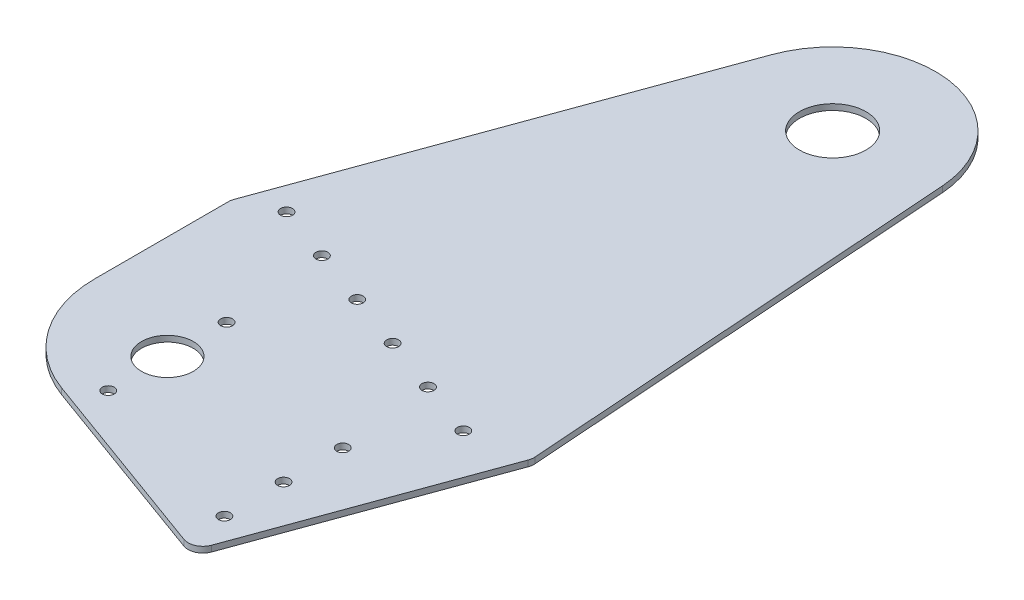
SolidWorks part; units mm, degrees
material "5052-H32"
ref_plane "Front Plane" through (0, 0, 0) normal (0, 0, 1) x (1, 0, 0)
ref_plane "Top Plane" through (0, 0, 0) normal (0, 1, 0) x (1, 0, 0)
ref_plane "Right Plane" through (0, 0, 0) normal (1, 0, 0) x (0, 0, -1)
sketch "Sketch1" plane through (0, 0, 0) normal (0, 1, 0) x (1, 0, 0)
  line L2 (0, 79.9615) -> (0, 137.226)
  line L3 (160.847, 106.8323) -> (8.6873, 162.2139) construction
  line L9 (124.1351, 5.967) -> (160.3844, 105.5611)
  line L11 (0, 138.3457) -> (152.1597, 82.9641) construction
  line L12 (4.3437, 150.2798) -> (156.5034, 94.8982) construction
  line L13 (116.079, 82.9641) -> (116.079, 0) construction
  line L14 (128.779, 6.7641) -> (103.379, 6.7641) construction
  line L15 (128.779, 6.7641) -> (128.779, 82.9641) construction
  line L16 (128.779, 82.9641) -> (103.379, 82.9641) construction
  line L17 (103.379, 6.7641) -> (103.379, 82.9641) construction
  line L18 (128.779, 6.7641) -> (103.379, 82.9641) construction
  line L19 (128.779, 82.9641) -> (103.379, 6.7641) construction
  line L20 (0.383, 139.3979) -> (8.6873, 162.2139)
  line L21 (8.6873, 162.2139) -> (61.8971, 308.4066)
  line L22 (147.4128, 296.4285) -> (160.7514, 108.1817)
  line L23 (33.4254, 32.2252) -> (115.9962, 2.1718)
  line L24 (0, 0) -> (121.9633, 0) construction
  circle A0 centre (103.379, 293.3084) radius 14.2875
  circle A1 centre (44.45, 66.6217) radius 11.1125
  circle A2 centre (44.45, 66.6217) radius 25.4 construction
  circle A3 centre (44.45, 92.0217) radius 2.5527
  circle A4 centre (44.45, 41.2217) radius 2.5527
  circle A5 centre (44.45, 66.6217) radius 31.75 construction
  arc A6 (147.4128, 296.4285) -> (61.8971, 308.4066) centre (103.379, 293.3084) ccw
  arc A9 (0.383, 139.3979) -> (0, 137.226) centre (6.35, 137.226) ccw
  arc A10 (160.3844, 105.5611) -> (160.7514, 108.1817) centre (154.4173, 107.7329) ccw
  arc A11 (115.9962, 2.1718) -> (124.1351, 5.967) centre (118.168, 8.1389) ccw
  arc A12 (0, 79.9615) -> (33.4254, 32.2252) centre (50.8, 79.9615) ccw
  point P3 (111.7505, 111.1869)
  point P14 (135.6187, 102.4996)
  point P20 (116.079, 44.8641)
  point P24 (87.8823, 119.8742)
  point P26 (64.0141, 128.5615)
  point P28 (40.1459, 137.2488)
  point P29 (116.079, 19.4641)
  point P32 (16.2778, 145.9362)
  point P42 (0, 0)
  point P49 (116.079, 70.2641)
  dimension "D2" = 28.575
  dimension "D3" = 22.225
  dimension "D4" = 50.8
  dimension "D5" = 5.1054
  dimension "D21" = 63.5
  dimension "D22" = 6.35
  dimension "D26" = 50.8
  dimension "D6" = 20
  dimension "D7" = 25.4
  dimension "D8" = 23.3807
  dimension "D9" = 161.925
  dimension "D10" = 25.4
  dimension "D11" = 12.7
  dimension "D12" = 155.575
  dimension "D13" = 25.4
  dimension "D14" = 25.4
  dimension "D15" = 25.4
  dimension "D16" = 25.4
  dimension "D17" = 234.221
  dimension "D18" = 44.45
  dimension "D19" = 25.4
  dimension "D20" = 76.2
  dimension "D23" = 25.4
  dimension "D24" = 25.4
  dimension "D25" = 12.7
  dimension "D27" = 77.5957
extrude "Boss-Extrude1" add sketch "Sketch1" along normal blind 2.54
hole_wizard "#7 (0.201) Diameter Hole1" positions "Sketch2" profile "Sketch3" hole size "#7" standard "ANSI Inch" end condition through all
sketch "Sketch2" plane through (0, 0, 0) normal (0, -1, 0) x (-1, 0, 0)
  point P0 (-135.6187, 102.4996)
  point P3 (-111.7505, 111.1869)
  point P6 (-87.8823, 119.8742)
  point P9 (-64.0141, 128.5615)
  point P12 (-40.1459, 137.2488)
  point P15 (-16.2778, 145.9362)
  point P18 (-116.079, 70.2641)
  point P21 (-116.079, 44.8641)
  point P24 (-116.079, 19.4641)
sketch "Sketch3" plane through (135.6187, 0, -102.4996) normal (1, 0, 0) x (0, 0, -1)
  line L0 (0, 0) -> (0, 2.54)
  line L1 (0, 2.54) -> (2.5527, 2.54)
  line L2 (2.5527, 2.54) -> (2.5527, 0)
  line L5 (2.5527, 0) -> (0, 0)
  line L11 (0, -6.35) -> (0, 107.95) construction
  dimension "Thru Hole Dia." = 5.1054
  dimension "Thru Hole Depth" = 2.54
sketch "Sketch7" [suppressed] plane through (0, 3.175, 0) normal (0, 1, 0) x (1, 0, 0)
  line L0 (62.0761, 169.3899) -> (62.5144, 170.567)
  line L1 (62.5144, 170.567) -> (61.5867, 170.2622)
  line L2 (66.9677, 175.195) -> (66.4796, 174.6886)
  line L3 (79.1731, 159.2722) -> (81.2123, 160.0556)
  line L4 (81.2123, 160.0556) -> (81.5639, 159.3016)
  line L5 (115.2098, 163.8413) -> (116.357, 163.4486)
  line L6 (116.357, 163.4486) -> (115.8813, 162.1889)
  line L7 (107.7827, 167.4695) -> (106.2875, 167.7994)
  line L8 (106.2875, 167.7994) -> (107.2664, 168.7114)
  line L9 (96.7548, 171.953) -> (96.1723, 172.7991)
  line L10 (96.1723, 172.7991) -> (95.6669, 171.9454)
  line L11 (100.3403, 166.7321) -> (97.6686, 163.2228)
  line L12 (89.4476, 166.3552) -> (91.3642, 168.2161)
  line L13 (91.3642, 168.2161) -> (90.6316, 168.886)
  line L14 (14.1169, 177.1315) -> (159.6183, 124.1733) construction
  line L15 (61.8971, 308.4066) -> (0.383, 139.3979) construction
  line L16 (160.7514, 108.1817) -> (147.4128, 296.4285) construction
  line L17 (33.4254, 32.2252) -> (115.9962, 2.1718) construction
  arc A0 (74.3082, 182.8504) -> (73.725, 182.5147) centre (74.7103, 181.4774) ccw
  arc A1 (73.725, 182.5147) -> (72.1718, 181.0017) centre (133.1992, 119.9033) ccw
  arc A2 (72.1718, 181.0017) -> (70.5314, 179.2921) centre (111.5899, 141.5378) ccw
  arc A3 (70.5314, 179.2921) -> (69.0762, 177.6244) centre (101.8392, 150.5038) ccw
  arc A4 (68.547, 177.0625) -> (69.0762, 177.6244) centre (64.4257, 181.474) ccw
  arc A5 (68.1985, 176.9514) -> (68.547, 177.0625) centre (68.2556, 177.3744) ccw
  arc A6 (67.7948, 177.1281) -> (68.1985, 176.9514) centre (68.3059, 177.7466) ccw
  arc A7 (66.8738, 177.9219) -> (67.7948, 177.1281) centre (86.4277, 199.6753) ccw
  arc A8 (66.8738, 177.9219) -> (65.9604, 178.4972) centre (64.7429, 175.5513) ccw
  arc A9 (65.9604, 178.4972) -> (64.9049, 178.7371) centre (64.7273, 175.5134) ccw
  arc A10 (64.9049, 178.7371) -> (63.6726, 178.6312) centre (64.6624, 174.336) ccw
  arc A11 (63.6726, 178.6312) -> (62.2317, 178.1778) centre (65.8385, 169.232) ccw
  arc A12 (62.2317, 178.1778) -> (60.6707, 177.4551) centre (68.6224, 162.3269) ccw
  arc A13 (60.6707, 177.4551) -> (59.5301, 176.703) centre (63.8858, 171.3384) ccw
  arc A14 (59.5301, 176.703) -> (58.5257, 175.7167) centre (64.2391, 170.9033) ccw
  arc A15 (58.5257, 175.7167) -> (57.3864, 174.2438) centre (75.6018, 161.3305) ccw
  arc A16 (56.7062, 173.3435) -> (57.3864, 174.2438) centre (42.2162, 184.9983) ccw
  arc A17 (56.1228, 172.7101) -> (56.7062, 173.3435) centre (51.6914, 177.3771) ccw
  arc A18 (55.5639, 172.2634) -> (56.1228, 172.7101) centre (53.2294, 175.7573) ccw
  arc A19 (54.9666, 171.9461) -> (55.5639, 172.2634) centre (53.6962, 175.0587) ccw
  arc A20 (54.5243, 171.7924) -> (54.9666, 171.9461) centre (53.293, 176.0466) ccw
  arc A21 (54.1163, 171.7066) -> (54.5243, 171.7924) centre (53.7472, 174.4772) ccw
  arc A22 (53.7901, 171.6904) -> (54.1163, 171.7066) centre (53.8553, 173.6659) ccw
  arc A23 (53.635, 171.7688) -> (53.7901, 171.6904) centre (53.7969, 171.8965) ccw
  arc A24 (53.5905, 172.1698) -> (53.635, 171.7688) centre (53.9344, 172.005) ccw
  arc A25 (54.0093, 172.8651) -> (53.5905, 172.1698) centre (57.4392, 170.3253) ccw
  arc A26 (54.9177, 173.9796) -> (54.0093, 172.8651) centre (66.4395, 163.6605) ccw
  arc A27 (56.8324, 176.0866) -> (54.9177, 173.9796) centre (201.8255, 42.4065) ccw
  arc A28 (56.8324, 176.0866) -> (58.6294, 178.1211) centre (10.0366, 219.2312) ccw
  arc A29 (58.6294, 178.1211) -> (59.308, 179.2325) centre (55.3883, 180.8631) ccw
  arc A30 (59.308, 179.2325) -> (59.3329, 180.0542) centre (58.2421, 179.6759) ccw
  arc A31 (59.3329, 180.0542) -> (58.8124, 180.8462) centre (57.5061, 179.4207) ccw
  arc A32 (58.8124, 180.8462) -> (57.7553, 181.5045) centre (56.5222, 178.3469) ccw
  arc A33 (57.7553, 181.5045) -> (56.6586, 181.6278) centre (56.9757, 179.5081) ccw
  arc A34 (56.6586, 181.6278) -> (55.3092, 181.1821) centre (57.2782, 177.4858) ccw
  arc A35 (55.3092, 181.1821) -> (53.3754, 180.0329) centre (66.6249, 159.9392) ccw
  arc A36 (50.4555, 178.11) -> (53.3754, 180.0329) centre (-1623.116, 2722.5471) ccw
  arc A37 (49.9624, 177.8143) -> (50.4555, 178.11) centre (46.648, 183.8988) ccw
  arc A38 (49.9101, 177.875) -> (49.9624, 177.8143) centre (49.9428, 177.8503) ccw
  arc A39 (50.3128, 178.3647) -> (49.9101, 177.875) centre (56.008, 173.2696) ccw
  arc A40 (50.6868, 178.776) -> (50.3128, 178.3647) centre (76.0211, 155.3656) ccw
  arc A41 (51.2355, 179.3665) -> (50.6868, 178.776) centre (157.5463, 80.0316) ccw
  arc A42 (51.843, 180.0132) -> (51.2355, 179.3665) centre (169.196, 69.1464) ccw
  arc A43 (52.4254, 180.6256) -> (51.843, 180.0132) centre (148.4427, 88.7526) ccw
  arc A44 (52.4254, 180.6256) -> (53.4057, 181.7377) centre (39.3118, 193.1732) ccw
  arc A45 (53.4057, 181.7377) -> (53.5985, 182.3391) centre (52.73, 182.286) ccw
  arc A46 (53.5985, 182.3391) -> (53.3133, 182.8365) centre (52.9532, 182.2996) ccw
  arc A47 (53.3133, 182.8365) -> (52.2525, 183.4524) centre (48.0293, 174.9565) ccw
  arc A48 (52.2525, 183.4524) -> (51.5201, 183.784) centre (47.2947, 173.4787) ccw
  arc A49 (51.5201, 183.784) -> (51.1138, 183.8533) centre (51.1621, 182.911) ccw
  arc A50 (51.1138, 183.8533) -> (50.7464, 183.7367) centre (51.1527, 183.0936) ccw
  arc A51 (50.7464, 183.7367) -> (50.2, 183.3471) centre (53.9544, 178.6599) ccw
  arc A52 (50.2, 183.3471) -> (49.7518, 182.9327) centre (52.8985, 179.9782) ccw
  arc A53 (49.7518, 182.9327) -> (49.0516, 182.1629) centre (73.6142, 160.5277) ccw
  arc A54 (49.0516, 182.1629) -> (48.2702, 181.2458) centre (76.593, 157.9039) ccw
  arc A55 (48.2702, 181.2458) -> (47.5086, 180.2915) centre (78.2622, 156.5282) ccw
  arc A56 (46.4851, 179.0185) -> (47.5086, 180.2915) centre (14.0592, 206.1378) ccw
  arc A57 (45.7613, 178.2653) -> (46.4851, 179.0185) centre (40.6676, 183.884) ccw
  arc A58 (45.0854, 177.7635) -> (45.7613, 178.2653) centre (42.8654, 181.4597) ccw
  arc A59 (44.2716, 177.3569) -> (45.0854, 177.7635) centre (42.0649, 182.7925) ccw
  arc A60 (42.4079, 176.7566) -> (44.2716, 177.3569) centre (39.29, 189.6277) ccw
  arc A61 (40.9063, 176.6373) -> (42.4079, 176.7566) centre (41.2837, 181.3973) ccw
  arc A62 (39.9018, 176.9889) -> (40.9063, 176.6373) centre (41.0714, 178.7199) ccw
  arc A63 (39.431, 177.7408) -> (39.9018, 176.9889) centre (40.5148, 177.8961) ccw
  arc A64 (39.5246, 178.6802) -> (39.431, 177.7408) centre (41.3834, 178.0206) ccw
  arc A65 (40.1422, 180.1498) -> (39.5246, 178.6802) centre (52.749, 173.9875) ccw
  arc A66 (40.967, 181.6069) -> (40.1422, 180.1498) centre (52.5933, 174.0636) ccw
  arc A67 (41.8093, 182.6065) -> (40.967, 181.6069) centre (45.3757, 178.7465) ccw
  arc A68 (42.735, 183.3116) -> (41.8093, 182.6065) centre (45.9761, 178.0966) ccw
  arc A69 (43.9637, 183.9848) -> (42.735, 183.3116) centre (49.4769, 172.4638) ccw
  arc A70 (45.1396, 184.492) -> (43.9637, 183.9848) centre (51.0302, 169.2179) ccw
  arc A71 (45.4706, 184.3586) -> (45.1396, 184.492) centre (45.2337, 184.2481) ccw
  arc A72 (45.4918, 184.1987) -> (45.4706, 184.3586) centre (45.2267, 184.2448) ccw
  arc A73 (45.4167, 183.8436) -> (45.4918, 184.1987) centre (40.5531, 185.0579) ccw
  arc A74 (45.2918, 183.4176) -> (45.4167, 183.8436) centre (40.1115, 185.1681) ccw
  arc A75 (45.1216, 182.9606) -> (45.2918, 183.4176) centre (37.7577, 185.9635) ccw
  arc A76 (44.6747, 182.1439) -> (45.1216, 182.9606) centre (41.315, 184.5129) ccw
  arc A77 (44.0662, 181.4742) -> (44.6747, 182.1439) centre (41.6698, 184.2628) ccw
  arc A78 (43.3406, 180.9981) -> (44.0662, 181.4742) centre (41.872, 184.0274) ccw
  arc A79 (42.5496, 180.7503) -> (43.3406, 180.9981) centre (42.1132, 183.5299) ccw
  arc A80 (42.5496, 180.7503) -> (42.0333, 180.6322) centre (43.1444, 176.9613) ccw
  arc A81 (42.0333, 180.6322) -> (41.6424, 180.4565) centre (42.5179, 179.0313) ccw
  arc A82 (41.6424, 180.4565) -> (41.3631, 180.2173) centre (42.2562, 179.4572) ccw
  arc A83 (41.3631, 180.2173) -> (41.1817, 179.91) centre (42.1574, 179.5413) ccw
  arc A84 (41.1817, 179.91) -> (41.3098, 179.5404) centre (41.4675, 179.802) ccw
  arc A85 (41.3098, 179.5404) -> (42.0184, 179.2356) centre (42.7766, 181.9744) ccw
  arc A86 (42.0184, 179.2356) -> (42.9911, 179.0785) centre (43.2169, 183.5653) ccw
  arc A87 (42.9911, 179.0785) -> (43.9333, 179.1484) centre (43.1825, 182.8819) ccw
  arc A88 (43.9333, 179.1484) -> (44.9037, 179.5156) centre (43.3041, 182.2773) ccw
  arc A89 (44.9037, 179.5156) -> (45.7482, 180.1858) centre (43.0455, 182.7238) ccw
  arc A90 (45.7482, 180.1858) -> (46.4656, 181.1717) centre (42.1809, 183.5357) ccw
  arc A91 (46.4656, 181.1717) -> (47.0588, 182.4767) centre (38.3652, 185.6409) ccw
  arc A92 (47.0588, 182.4767) -> (47.3717, 183.6741) centre (40.8285, 184.7444) ccw
  arc A93 (47.3717, 183.6741) -> (47.3128, 184.5787) centre (45.3846, 183.9991) ccw
  arc A94 (47.3128, 184.5787) -> (46.8711, 185.315) centre (45.6402, 184.0759) ccw
  arc A95 (46.8711, 185.315) -> (46.0042, 185.9854) centre (43.743, 182.166) ccw
  arc A96 (46.0042, 185.9854) -> (43.5248, 186.5796) centre (43.802, 182.2657) ccw
  arc A97 (43.5248, 186.5796) -> (40.6936, 185.808) centre (43.994, 179.2776) ccw
  arc A98 (40.6936, 185.808) -> (38.0435, 183.8254) centre (44.996, 177.2948) ccw
  arc A99 (38.0435, 183.8254) -> (36.1073, 180.9839) centre (46.1106, 176.2478) ccw
  arc A100 (35.7666, 180.3077) -> (36.1073, 180.9839) centre (22.1662, 187.5841) ccw
  arc A101 (35.4405, 179.7525) -> (35.7666, 180.3077) centre (28.6157, 184.1336) ccw
  arc A102 (35.1529, 179.3322) -> (35.4405, 179.7525) centre (28.1525, 184.4309) ccw
  arc A103 (35.0212, 179.292) -> (35.1529, 179.3322) centre (35.0603, 179.3996) ccw
  arc A104 (34.8987, 179.3634) -> (35.0212, 179.292) centre (35.1574, 179.6664) ccw
  arc A105 (34.7135, 179.5337) -> (34.8987, 179.3634) centre (37.1267, 181.9726) ccw
  arc A106 (34.5102, 179.7505) -> (34.7135, 179.5337) centre (37.4991, 182.3489) ccw
  arc A107 (34.3152, 179.9906) -> (34.5102, 179.7505) centre (38.0148, 182.7973) ccw
  arc A108 (34.3152, 179.9906) -> (33.9923, 180.3441) centre (32.2157, 178.3978) ccw
  arc A109 (33.9923, 180.3441) -> (33.1472, 181.1013) centre (-7.0589, 135.3727) ccw
  arc A110 (33.1472, 181.1013) -> (32.12, 181.9836) centre (-5.5235, 137.119) ccw
  arc A111 (32.12, 181.9836) -> (30.9902, 182.914) centre (-19.1906, 120.8302) ccw
  arc A112 (29.8644, 183.859) -> (30.9902, 182.914) centre (55.91, 213.7448) ccw
  arc A113 (28.849, 184.7853) -> (29.8644, 183.859) centre (49.7895, 206.7219) ccw
  arc A114 (28.0329, 185.5958) -> (28.849, 184.7853) centre (48.8821, 205.7713) ccw
  arc A115 (27.72, 186.0357) -> (28.0329, 185.5958) centre (29.3248, 186.846) ccw
  arc A116 (27.5634, 187.404) -> (27.72, 186.0357) centre (29.4953, 186.932) ccw
  arc A117 (28.2937, 188.8328) -> (27.5634, 187.404) centre (30.9404, 186.579) ccw
  arc A118 (29.9235, 190.2307) -> (28.2937, 188.8328) centre (33.5403, 184.365) ccw
  arc A119 (32.3635, 191.4887) -> (29.9235, 190.2307) centre (39.3462, 174.9492) ccw
  arc A120 (34.2055, 192.0999) -> (32.3635, 191.4887) centre (37.1375, 180.1808) ccw
  arc A121 (36.2347, 192.4587) -> (34.2055, 192.0999) centre (37.9264, 176.974) ccw
  arc A122 (38.0495, 192.5388) -> (36.2347, 192.4587) centre (37.761, 178.4879) ccw
  arc A123 (39.0536, 192.2197) -> (38.0495, 192.5388) centre (38.0113, 190.6797) ccw
  arc A124 (39.401, 191.9318) -> (39.0536, 192.2197) centre (37.7469, 190.289) ccw
  arc A125 (39.5146, 191.678) -> (39.401, 191.9318) centre (39.1218, 191.6545) ccw
  arc A126 (39.4565, 191.3418) -> (39.5146, 191.678) centre (38.7713, 191.6335) ccw
  arc A127 (39.1465, 190.6692) -> (39.4565, 191.3418) centre (27.8847, 196.2671) ccw
  arc A128 (38.0069, 188.9592) -> (39.1465, 190.6692) centre (31.8572, 194.2925) ccw
  arc A129 (36.3742, 187.4082) -> (38.0069, 188.9592) centre (29.1898, 196.6058) ccw
  arc A130 (34.4963, 186.2162) -> (36.3742, 187.4082) centre (29.3429, 196.4098) ccw
  arc A131 (32.6257, 185.5753) -> (34.4963, 186.2162) centre (31.2535, 192.6306) ccw
  arc A132 (32.6257, 185.5753) -> (32.326, 185.4734) centre (32.849, 184.4267) ccw
  arc A133 (32.326, 185.4734) -> (32.1971, 185.3132) centre (32.4364, 185.2526) ccw
  arc A134 (32.1971, 185.3132) -> (32.187, 185.0278) centre (32.8524, 185.1473) ccw
  arc A135 (32.187, 185.0278) -> (32.3205, 184.3701) centre (46.8553, 187.6615) ccw
  arc A136 (32.3205, 184.3701) -> (32.6327, 183.5397) centre (35.4909, 185.088) ccw
  arc A137 (32.6327, 183.5397) -> (33.1345, 182.9292) centre (34.4573, 184.5281) ccw
  arc A138 (33.1345, 182.9292) -> (33.7845, 182.5919) centre (34.2412, 184.2668) ccw
  arc A139 (33.7845, 182.5919) -> (34.5255, 182.546) centre (34.2659, 184.3575) ccw
  arc A140 (34.5255, 182.546) -> (36.1223, 183.2401) centre (34.0587, 185.8032) ccw
  arc A141 (36.1223, 183.2401) -> (38.2538, 185.2006) centre (22.3005, 200.4074) ccw
  arc A142 (38.2538, 185.2006) -> (40.2061, 187.5541) centre (22.1985, 200.5047) ccw
  arc A143 (40.2061, 187.5541) -> (41.3352, 189.6901) centre (33.0357, 192.7108) ccw
  arc A144 (41.3352, 189.6901) -> (41.6737, 191.3689) centre (35.9537, 191.6488) ccw
  arc A145 (41.6737, 191.3689) -> (41.4198, 192.8507) centre (38.2108, 191.5384) ccw
  arc A146 (41.4198, 192.8507) -> (40.543, 194.1499) centre (37.865, 191.397) ccw
  arc A147 (40.543, 194.1499) -> (39.0445, 195.2909) centre (35.0939, 188.5481) ccw
  arc A148 (39.0445, 195.2909) -> (36.5392, 195.9699) centre (36.5427, 191.021) ccw
  arc A149 (36.5392, 195.9699) -> (32.9739, 195.586) centre (36.5513, 179.1093) ccw
  arc A150 (32.9739, 195.586) -> (29.3635, 194.3985) centre (36.8595, 177.6898) ccw
  arc A151 (29.3635, 194.3985) -> (26.6543, 192.6008) centre (33.4359, 185.3211) ccw
  arc A152 (26.6543, 192.6008) -> (24.9307, 190.1375) centre (31.5632, 187.3313) ccw
  arc A153 (24.9307, 190.1375) -> (24.6835, 187.5211) centre (28.9468, 188.4382) ccw
  arc A154 (24.6835, 187.5211) -> (26.0207, 184.7839) centre (30.8844, 188.8551) ccw
  arc A155 (26.0207, 184.7839) -> (28.9405, 181.9734) centre (40.4964, 196.9008) ccw
  arc A156 (29.9885, 181.128) -> (28.9405, 181.9734) centre (8.4014, 155.4417) ccw
  arc A157 (30.3575, 180.6787) -> (29.9885, 181.128) centre (28.9675, 179.9132) ccw
  arc A158 (30.3713, 180.3133) -> (30.3575, 180.6787) centre (30.0009, 180.4823) ccw
  arc A159 (30.0759, 179.9118) -> (30.3713, 180.3133) centre (29.2641, 180.8183) ccw
  arc A160 (28.5512, 179.2654) -> (30.0759, 179.9118) centre (28.3681, 181.8189) ccw
  arc A161 (25.8887, 179.3109) -> (28.5512, 179.2654) centre (27.4758, 194.2586) ccw
  arc A162 (23.2563, 179.8312) -> (25.8887, 179.3109) centre (27.4762, 194.2617) ccw
  arc A163 (21.8803, 180.7864) -> (23.2563, 179.8312) centre (23.9984, 182.369) ccw
  arc A164 (21.8803, 180.7864) -> (21.4146, 181.3746) centre (11.131, 172.7548) ccw
  arc A165 (21.4146, 181.3746) -> (21.194, 181.4707) centre (21.208, 181.2014) ccw
  arc A166 (21.194, 181.4707) -> (20.9847, 181.3519) centre (21.2079, 181.2022) ccw
  arc A167 (20.9847, 181.3519) -> (20.5852, 180.7185) centre (32.0578, 173.9268) ccw
  arc A168 (20.5852, 180.7185) -> (20.5596, 178.2742) centre (22.6871, 179.4742) ccw
  arc A169 (20.5596, 178.2742) -> (22.7566, 176.3693) centre (24.3256, 180.3983) ccw
  arc A170 (22.7566, 176.3693) -> (26.8636, 175.665) centre (26.5339, 186.0688) ccw
  arc A171 (26.8636, 175.665) -> (31.4496, 176.4875) centre (26.3557, 191.6925) ccw
  arc A172 (32.2098, 176.7264) -> (31.4496, 176.4875) centre (38.1788, 156.4012) ccw
  arc A173 (33.0182, 176.9497) -> (32.2098, 176.7264) centre (39.5156, 151.8489) ccw
  arc A174 (33.7585, 177.1285) -> (33.0182, 176.9497) centre (38.8624, 154.3726) ccw
  arc A175 (34.2819, 177.2207) -> (33.7585, 177.1285) centre (35.0169, 171.5178) ccw
  arc A176 (34.9396, 177.2772) -> (34.2819, 177.2207) centre (35.2749, 169.5161) ccw
  arc A177 (35.2649, 177.2034) -> (34.9396, 177.2772) centre (34.967, 176.6436) ccw
  arc A178 (35.5206, 176.9724) -> (35.2649, 177.2034) centre (34.9322, 176.5782) ccw
  arc A179 (35.9024, 176.3582) -> (35.5206, 176.9724) centre (26.6812, 171.0512) ccw
  arc A180 (35.9024, 176.3582) -> (36.9988, 175.1864) centre (38.9535, 178.1142) ccw
  arc A181 (36.9988, 175.1864) -> (38.571, 174.5314) centre (39.4525, 178.8615) ccw
  arc A182 (38.571, 174.5314) -> (40.5484, 174.4493) centre (39.8152, 180.6435) ccw
  arc A183 (40.5484, 174.4493) -> (42.8178, 174.9505) centre (39.1738, 186.0622) ccw
  arc A184 (43.3201, 175.1069) -> (42.8178, 174.9505) centre (48.2695, 158.3264) ccw
  arc A185 (43.7701, 175.2291) -> (43.3201, 175.1069) centre (46.3835, 164.7208) ccw
  arc A186 (44.1476, 175.3175) -> (43.7701, 175.2291) centre (47.1628, 161.587) ccw
  arc A187 (44.2628, 175.3098) -> (44.1476, 175.3175) centre (44.192, 175.1153) ccw
  arc A188 (44.3107, 175.241) -> (44.2628, 175.3098) centre (44.2379, 175.2415) ccw
  arc A189 (44.2954, 175.0356) -> (44.3107, 175.241) centre (42.7889, 175.2514) ccw
  arc A190 (44.2393, 174.7674) -> (44.2954, 175.0356) centre (42.1713, 175.3398) ccw
  arc A191 (44.1412, 174.4607) -> (44.2393, 174.7674) centre (40.311, 175.8548) ccw
  arc A192 (44.1412, 174.4607) -> (44.0089, 173.708) centre (46.203, 173.7103) ccw
  arc A193 (44.0089, 173.708) -> (44.1385, 172.9419) centre (46.3511, 173.7104) ccw
  arc A194 (44.1385, 172.9419) -> (44.5028, 172.2883) centre (46.1785, 173.6505) ccw
  arc A195 (44.5028, 172.2883) -> (45.0452, 171.8581) centre (45.7458, 173.2987) ccw
  arc A196 (45.0452, 171.8581) -> (45.5046, 171.7887) centre (45.3862, 172.5592) ccw
  arc A197 (45.5046, 171.7887) -> (46.0003, 171.9763) centre (45.311, 173.0486) ccw
  arc A198 (46.0003, 171.9763) -> (46.7213, 172.5276) centre (42.9825, 176.6707) ccw
  arc A199 (46.7213, 172.5276) -> (48.1908, 173.8802) centre (-21.0634, 247.6437) ccw
  arc A200 (49.9531, 175.4754) -> (48.1908, 173.8802) centre (92.8617, 126.3005) ccw
  arc A201 (51.74, 176.975) -> (49.9531, 175.4754) centre (89.7982, 129.8115) ccw
  arc A202 (53.4092, 178.3032) -> (51.74, 176.975) centre (149.5534, 55.76) ccw
  arc A203 (53.7366, 178.3554) -> (53.4092, 178.3032) centre (53.6199, 178.0346) ccw
  arc A204 (53.756, 178.2996) -> (53.7366, 178.3554) centre (53.7236, 178.3196) ccw
  arc A205 (53.4455, 177.8028) -> (53.756, 178.2996) centre (14.1169, 202.725) ccw
  arc A206 (53.0612, 177.2191) -> (53.4455, 177.8028) centre (36.5165, 188.5306) ccw
  arc A207 (52.5822, 176.5337) -> (53.0612, 177.2191) centre (19.3352, 200.2773) ccw
  arc A208 (52.5822, 176.5337) -> (51.6189, 175.0333) centre (67.2678, 166.0458) ccw
  arc A209 (51.6189, 175.0333) -> (50.8843, 173.5493) centre (63.2726, 168.3404) ccw
  arc A210 (50.8843, 173.5493) -> (50.4332, 172.233) centre (60.3416, 169.5728) ccw
  arc A211 (50.4332, 172.233) -> (50.3764, 171.2877) centre (52.709, 171.622) ccw
  arc A212 (50.3764, 171.2877) -> (50.8293, 170.4134) centre (51.8564, 171.4998) ccw
  arc A213 (50.8293, 170.4134) -> (51.7794, 169.8973) centre (52.2752, 171.9427) ccw
  arc A214 (51.7794, 169.8973) -> (53.1461, 169.8276) centre (52.647, 173.4767) ccw
  arc A215 (53.1461, 169.8276) -> (54.7542, 170.2266) centre (52.0974, 177.4948) ccw
  arc A216 (55.3189, 170.4157) -> (54.7542, 170.2266) centre (58.4979, 159.9846) ccw
  arc A217 (55.6177, 170.4524) -> (55.3189, 170.4157) centre (55.573, 169.5819) ccw
  arc A218 (55.7691, 170.3669) -> (55.6177, 170.4524) centre (55.6077, 170.2581) ccw
  arc A219 (55.8258, 170.1715) -> (55.7691, 170.3669) centre (55.4927, 170.1806) ccw
  arc A220 (55.8258, 170.1715) -> (55.8514, 169.9319) centre (56.7312, 170.1468) ccw
  arc A221 (55.8514, 169.9319) -> (55.9579, 169.5508) centre (61.6551, 171.3493) ccw
  arc A222 (55.9579, 169.5508) -> (56.1102, 169.1191) centre (62.5193, 171.6221) ccw
  arc A223 (56.1102, 169.1191) -> (56.2928, 168.6924) centre (62.8661, 171.7576) ccw
  arc A224 (56.2928, 168.6924) -> (57.4829, 167.4515) centre (58.71, 169.8196) ccw
  arc A225 (57.4829, 167.4515) -> (59.2339, 167.1346) centre (58.8722, 170.1326) ccw
  arc A226 (59.2339, 167.1346) -> (60.9662, 167.8594) centre (58.8215, 170.5531) ccw
  arc A227 (60.9662, 167.8594) -> (62.0761, 169.3899) centre (58.7665, 170.6222) ccw
  arc A228 (60.6138, 170.7928) -> (61.5867, 170.2622) centre (61.3494, 170.9844) ccw
  arc A229 (60.8154, 172.4171) -> (60.6138, 170.7928) centre (62.7575, 171.3513) ccw
  arc A230 (62.6398, 174.8337) -> (60.8154, 172.4171) centre (70.0177, 167.367) ccw
  arc A231 (64.8718, 176.2485) -> (62.6398, 174.8337) centre (67.003, 170.418) ccw
  arc A232 (65.3282, 176.4029) -> (64.8718, 176.2485) centre (68.2976, 166.8761) ccw
  arc A233 (65.749, 176.5194) -> (65.3282, 176.4029) centre (67.3605, 169.8827) ccw
  arc A234 (66.1032, 176.5955) -> (65.749, 176.5194) centre (67.3446, 169.9483) ccw
  arc A235 (66.2518, 176.5832) -> (66.1032, 176.5955) centre (66.1551, 176.3175) ccw
  arc A236 (66.44, 176.4345) -> (66.2518, 176.5832) centre (66.1213, 176.2247) ccw
  arc A237 (66.7316, 175.9559) -> (66.44, 176.4345) centre (59.7592, 172.036) ccw
  arc A238 (66.9914, 175.457) -> (66.7316, 175.9559) centre (59.0868, 171.658) ccw
  arc A239 (67.0017, 175.2495) -> (66.9914, 175.457) centre (66.7501, 175.3411) ccw
  arc A240 (66.9677, 175.195) -> (67.0017, 175.2495) centre (66.8559, 175.3025) ccw
  arc A241 (65.9217, 174.1157) -> (66.4796, 174.6886) centre (-0.3358, 239.1998) ccw
  arc A242 (65.2645, 173.4503) -> (65.9217, 174.1157) centre (-57.3273, 295.182) ccw
  arc A243 (65.2645, 173.4503) -> (64.0677, 172.1499) centre (81.8084, 157.0225) ccw
  arc A244 (64.0677, 172.1499) -> (63.4286, 171.1774) centre (67.6274, 169.1145) ccw
  arc A245 (63.4286, 171.1774) -> (63.0742, 170.1165) centre (67.1785, 169.3351) ccw
  arc A246 (63.0742, 170.1165) -> (62.8538, 168.5433) centre (79.0298, 167.0787) ccw
  arc A247 (62.8538, 168.5433) -> (62.9704, 166.7394) centre (68.6902, 168.0148) ccw
  arc A248 (62.9704, 166.7394) -> (63.6889, 165.5617) centre (65.0575, 167.2048) ccw
  arc A249 (63.6889, 165.5617) -> (64.9741, 165.071) centre (65.0485, 167.194) ccw
  arc A250 (64.9741, 165.071) -> (66.7601, 165.2889) centre (65.1764, 170.8417) ccw
  arc A251 (67.3237, 165.441) -> (66.7601, 165.2889) centre (72.4207, 145.443) ccw
  arc A252 (67.8029, 165.5512) -> (67.3237, 165.441) centre (69.904, 155.3172) ccw
  arc A253 (68.2017, 165.6286) -> (67.8029, 165.5512) centre (71.5525, 147.2877) ccw
  arc A254 (68.2539, 165.5956) -> (68.2017, 165.6286) centre (68.2099, 165.5838) ccw
  arc A255 (68.2632, 165.5138) -> (68.2539, 165.5956) centre (67.9851, 165.5235) ccw
  arc A256 (68.2486, 165.1392) -> (68.2632, 165.5138) centre (18.2975, 167.2726) ccw
  arc A257 (68.2263, 164.699) -> (68.2486, 165.1392) centre (40.5629, 166.3217) ccw
  arc A258 (68.1942, 164.1979) -> (68.2263, 164.699) centre (21.7421, 167.4257) ccw
  arc A259 (68.1942, 164.1979) -> (68.2557, 162.9509) centre (73.4553, 163.8323) ccw
  arc A260 (68.2557, 162.9509) -> (68.6061, 161.6871) centre (74.5732, 164.0218) ccw
  arc A261 (68.6061, 161.6871) -> (69.1861, 160.5706) centre (74.1315, 163.849) ccw
  arc A262 (69.1861, 160.5706) -> (69.9292, 159.7637) centre (72.0774, 162.4873) ccw
  arc A263 (69.9292, 159.7637) -> (71.0506, 159.11) centre (72.8077, 163.4132) ccw
  arc A264 (71.0506, 159.11) -> (72.6135, 158.5966) centre (75.4812, 169.9608) ccw
  arc A265 (72.6135, 158.5966) -> (74.2686, 158.2998) centre (75.5651, 170.2933) ccw
  arc A266 (74.2686, 158.2998) -> (75.6874, 158.3104) centre (74.932, 164.4372) ccw
  arc A267 (75.6874, 158.3104) -> (76.3847, 158.4332) centre (74.8472, 165.1251) ccw
  arc A268 (76.3847, 158.4332) -> (77.308, 158.6665) centre (71.4689, 179.8295) ccw
  arc A269 (77.308, 158.6665) -> (78.2865, 158.9591) centre (70.9596, 181.6752) ccw
  arc A270 (78.2865, 158.9591) -> (79.1731, 159.2722) centre (73.0176, 175.2945) ccw
  arc A271 (81.5639, 159.3016) -> (82.0723, 158.5817) centre (83.8133, 160.3506) ccw
  arc A272 (82.0723, 158.5817) -> (82.8503, 157.998) centre (84.6282, 161.1785) ccw
  arc A273 (82.8503, 157.998) -> (83.7221, 157.6587) centre (84.503, 160.9544) ccw
  arc A274 (83.7221, 157.6587) -> (84.5041, 157.658) centre (84.1145, 159.3147) ccw
  arc A275 (84.5041, 157.658) -> (84.898, 157.7963) centre (84.055, 159.5674) ccw
  arc A276 (84.898, 157.7963) -> (85.4779, 158.094) centre (80.2438, 167.5753) ccw
  arc A277 (85.4779, 158.094) -> (86.1162, 158.4718) centre (79.4906, 168.9396) ccw
  arc A278 (86.1162, 158.4718) -> (86.7275, 158.8854) centre (79.669, 168.6578) ccw
  arc A279 (87.2967, 159.2808) -> (86.7275, 158.8854) centre (97.7406, 143.6379) ccw
  arc A280 (87.8098, 159.6034) -> (87.2967, 159.2808) centre (93.4193, 150.1105) ccw
  arc A281 (88.2441, 159.8499) -> (87.8098, 159.6034) centre (95.1182, 147.2354) ccw
  arc A282 (88.3811, 159.8626) -> (88.2441, 159.8499) centre (88.3273, 159.6972) ccw
  arc A283 (88.4414, 159.7807) -> (88.3811, 159.8626) centre (88.3541, 159.7795) ccw
  arc A284 (88.427, 159.5386) -> (88.4414, 159.7807) centre (86.7915, 159.7576) ccw
  arc A285 (88.3624, 159.22) -> (88.427, 159.5386) centre (86.0178, 159.8612) ccw
  arc A286 (88.2462, 158.8546) -> (88.3624, 159.22) centre (83.8571, 160.4521) ccw
  arc A287 (88.2462, 158.8546) -> (88.1272, 158.3962) centre (90.5899, 158.0016) ccw
  arc A288 (88.1272, 158.3962) -> (88.0913, 157.9067) centre (90.9602, 157.9422) ccw
  arc A289 (88.0913, 157.9067) -> (88.1393, 157.4142) centre (91.0105, 157.9429) ccw
  arc A290 (88.1393, 157.4142) -> (88.2697, 156.946) centre (90.8101, 157.906) ccw
  arc A291 (88.2697, 156.946) -> (88.5079, 156.4198) centre (92.5095, 158.5481) ccw
  arc A292 (88.5079, 156.4198) -> (88.7537, 156.1203) centre (89.3753, 156.8811) ccw
  arc A293 (88.7537, 156.1203) -> (89.0958, 155.9389) centre (89.378, 156.8844) ccw
  arc A294 (89.0958, 155.9389) -> (89.6608, 155.8086) centre (90.4086, 160.338) ccw
  arc A295 (89.6608, 155.8086) -> (90.1565, 155.7817) centre (90.0307, 158.0495) ccw
  arc A296 (90.1565, 155.7817) -> (90.8132, 155.8497) centre (89.7737, 162.6832) ccw
  arc A297 (90.8132, 155.8497) -> (91.5106, 155.9893) centre (89.6645, 163.4011) ccw
  arc A298 (91.5106, 155.9893) -> (92.1441, 156.1863) centre (90.1128, 161.6014) ccw
  arc A299 (93.2212, 156.5738) -> (92.1441, 156.1863) centre (107.0085, 116.5611) ccw
  arc A300 (93.653, 156.6471) -> (93.2212, 156.5738) centre (93.6592, 155.3025) ccw
  arc A301 (93.8054, 156.5151) -> (93.653, 156.6471) centre (93.6537, 156.494) ccw
  arc A302 (93.7714, 156.1938) -> (93.8054, 156.5151) centre (93.1422, 156.4228) ccw
  arc A303 (93.7714, 156.1938) -> (93.7529, 155.6122) centre (94.648, 155.8748) ccw
  arc A304 (93.7529, 155.6122) -> (94.0829, 154.8096) centre (97.7329, 156.7795) ccw
  arc A305 (94.0829, 154.8096) -> (94.5832, 154.0778) centre (97.8126, 156.8225) ccw
  arc A306 (94.5832, 154.0778) -> (95.112, 153.71) centre (95.5427, 154.8932) ccw
  arc A307 (95.112, 153.71) -> (96.1172, 153.5975) centre (95.8467, 155.7286) ccw
  arc A308 (96.1172, 153.5975) -> (97.5577, 153.9024) centre (94.9894, 162.4836) ccw
  arc A309 (97.5577, 153.9024) -> (99.0889, 154.4962) centre (94.5811, 163.8479) ccw
  arc A310 (99.0889, 154.4962) -> (100.4205, 155.2988) centre (95.4623, 162.0198) ccw
  arc A311 (100.4205, 155.2988) -> (101.005, 155.7598) centre (93.571, 164.5834) ccw
  arc A312 (101.005, 155.7598) -> (101.4861, 156.2055) centre (96.5124, 161.0922) ccw
  arc A313 (101.4861, 156.2055) -> (101.8369, 156.5933) centre (96.9623, 160.6501) ccw
  arc A314 (101.8369, 156.5933) -> (101.8862, 156.7905) centre (101.657, 156.743) ccw
  arc A315 (101.8862, 156.7905) -> (101.6772, 157.1413) centre (101.2743, 156.6636) ccw
  arc A316 (101.6772, 157.1413) -> (101.3093, 157.2626) centre (101.3422, 156.7441) ccw
  arc A317 (101.3093, 157.2626) -> (100.7828, 157.1091) centre (101.3888, 156.0107) ccw
  arc A318 (100.7828, 157.1091) -> (100.1358, 156.6795) centre (103.0724, 152.9588) ccw
  arc A319 (99.2924, 156.1129) -> (100.1358, 156.6795) centre (96.0217, 161.8922) ccw
  arc A320 (98.3794, 155.687) -> (99.2924, 156.1129) centre (96.1294, 161.7019) ccw
  arc A321 (97.5854, 155.4596) -> (98.3794, 155.687) centre (96.5488, 160.5808) ccw
  arc A322 (97.2265, 155.5913) -> (97.5854, 155.4596) centre (97.513, 155.8174) ccw
  arc A323 (97.1513, 156.3756) -> (97.2265, 155.5913) centre (97.7972, 156.0417) ccw
  arc A324 (98.3117, 158.4158) -> (97.1513, 156.3756) centre (123.2009, 142.9097) ccw
  arc A325 (100.0065, 160.8692) -> (98.3117, 158.4158) centre (125.0369, 141.7659) ccw
  arc A326 (102.1792, 163.5408) -> (100.0065, 160.8692) centre (144.3604, 127.018) ccw
  arc A327 (103.5171, 165.0485) -> (102.1792, 163.5408) centre (164.7872, 109.3315) ccw
  arc A328 (104.2773, 165.7708) -> (103.5171, 165.0485) centre (108.8368, 160.211) ccw
  arc A329 (104.8168, 166.0837) -> (104.2773, 165.7708) centre (105.5083, 164.2697) ccw
  arc A330 (105.2843, 166.0873) -> (104.8168, 166.0837) centre (105.0553, 165.458) ccw
  arc A331 (105.3465, 165.9273) -> (105.2843, 166.0873) centre (105.2453, 165.98) ccw
  arc A332 (105.0939, 165.5331) -> (105.3465, 165.9273) centre (103.0097, 167.1464) ccw
  arc A333 (104.5868, 164.9464) -> (105.0939, 165.5331) centre (99.4276, 169.919) ccw
  arc A334 (103.7536, 164.1096) -> (104.5868, 164.9464) centre (78.4434, 190.1439) ccw
  arc A335 (103.7536, 164.1096) -> (102.3738, 162.6584) centre (121.5081, 145.8473) ccw
  arc A336 (102.3738, 162.6584) -> (101.6815, 161.5964) centre (105.712, 159.7254) ccw
  arc A337 (101.6815, 161.5964) -> (101.4294, 160.5657) centre (104.1682, 160.4421) ccw
  arc A338 (101.4294, 160.5657) -> (101.5169, 159.2913) centre (107.0552, 160.3118) ccw
  arc A339 (101.5169, 159.2913) -> (102.0068, 157.7779) centre (107.5122, 160.396) ccw
  arc A340 (102.0068, 157.7779) -> (102.9056, 156.2974) centre (109.7048, 161.4387) ccw
  arc A341 (102.9056, 156.2974) -> (104.2497, 154.8037) centre (112.3119, 163.41) ccw
  arc A342 (104.2497, 154.8037) -> (106.0867, 153.2478) centre (120.7155, 172.3809) ccw
  arc A343 (107.1588, 152.2758) -> (106.0867, 153.2478) centre (100.8303, 146.373) ccw
  arc A344 (107.2427, 151.6389) -> (107.1588, 152.2758) centre (106.7543, 151.8985) ccw
  arc A345 (106.625, 151.1698) -> (107.2427, 151.6389) centre (106.4259, 152.0731) ccw
  arc A346 (104.8179, 150.8612) -> (106.625, 151.1698) centre (102.4977, 169.8959) ccw
  arc A347 (102.932, 150.7695) -> (104.8179, 150.8612) centre (103.2457, 163.759) ccw
  arc A348 (101.2302, 150.9765) -> (102.932, 150.7695) centre (103.146, 159.6295) ccw
  arc A349 (99.8263, 151.4569) -> (101.2302, 150.9765) centre (102.6676, 157.4686) ccw
  arc A350 (98.8346, 152.1859) -> (99.8263, 151.4569) centre (101.2015, 154.3666) ccw
  arc A351 (98.8346, 152.1859) -> (98.2533, 152.7414) centre (94.1824, 147.8996) ccw
  arc A352 (98.2533, 152.7414) -> (97.9025, 152.8128) centre (98.0124, 152.455) ccw
  arc A353 (97.9025, 152.8128) -> (97.6086, 152.5576) centre (98.0436, 152.3534) ccw
  arc A354 (97.6086, 152.5576) -> (97.2521, 151.7001) centre (106.9734, 148.1619) ccw
  arc A355 (97.2521, 151.7001) -> (97.5139, 149.4925) centre (99.5718, 150.8558) ccw
  arc A356 (97.5139, 149.4925) -> (99.5568, 147.833) centre (101.185, 151.9245) ccw
  arc A357 (99.5568, 147.833) -> (103.1248, 147.1564) centre (103.0872, 156.7047) ccw
  arc A358 (103.1248, 147.1564) -> (107.3336, 147.6883) centre (103.0561, 164.6175) ccw
  arc A359 (107.3336, 147.6883) -> (108.1157, 147.8984) centre (100.7179, 173.8716) ccw
  arc A360 (108.1157, 147.8984) -> (108.8582, 148.1237) centre (101.8914, 169.7516) ccw
  arc A361 (108.8582, 148.1237) -> (109.4811, 148.3352) centre (102.4455, 168.0313) ccw
  arc A362 (109.4811, 148.3352) -> (109.7929, 148.4805) centre (108.8578, 150.0801) ccw
  arc A363 (110.551, 148.7041) -> (109.7929, 148.4805) centre (110.6245, 147.058) ccw
  arc A364 (111.4377, 148.592) -> (110.551, 148.7041) centre (110.6686, 146.0707) ccw
  arc A365 (112.3117, 148.1686) -> (111.4377, 148.592) centre (110.5204, 145.5849) ccw
  arc A366 (113.0306, 147.4929) -> (112.3117, 148.1686) centre (110.4085, 145.4234) ccw
  arc A367 (113.0306, 147.4929) -> (114.0876, 146.5636) centre (116.0922, 149.9093) ccw
  arc A368 (114.0876, 146.5636) -> (115.4418, 146.0301) centre (116.3711, 150.3749) ccw
  arc A369 (115.4418, 146.0301) -> (117.0635, 145.9201) centre (116.6348, 151.6077) ccw
  arc A370 (117.0635, 145.9201) -> (118.9045, 146.2365) centre (116.3233, 155.7421) ccw
  arc A371 (119.6917, 146.4433) -> (118.9045, 146.2365) centre (131.9567, 98.1706) ccw
  arc A372 (120.3794, 146.609) -> (119.6917, 146.4433) centre (126.7001, 118.8596) ccw
  arc A373 (120.9676, 146.7397) -> (120.3794, 146.609) centre (133.1775, 90.4219) ccw
  arc A374 (121.0804, 146.7321) -> (120.9676, 146.7397) centre (121.0107, 146.5407) ccw
  arc A375 (121.1231, 146.6671) -> (121.0804, 146.7321) centre (121.0581, 146.6709) ccw
  arc A376 (121.0986, 146.4529) -> (121.1231, 146.6671) centre (119.1481, 146.784) ccw
  arc A377 (121.0356, 146.1763) -> (121.0986, 146.4529) centre (118.6024, 146.8766) ccw
  arc A378 (120.9321, 145.8584) -> (121.0356, 146.1763) centre (116.3671, 147.5199) ccw
  arc A379 (120.9321, 145.8584) -> (120.8158, 145.1098) centre (122.7691, 145.1898) ccw
  arc A380 (120.8158, 145.1098) -> (120.9839, 144.3398) centre (123.0909, 145.2029) ccw
  arc A381 (120.9839, 144.3398) -> (121.3948, 143.698) centre (122.9451, 145.1432) ccw
  arc A382 (121.3948, 143.698) -> (121.9741, 143.3145) centre (122.4829, 144.7123) ccw
  arc A383 (121.9741, 143.3145) -> (122.4116, 143.2933) centre (122.227, 144.0094) ccw
  arc A384 (122.4116, 143.2933) -> (122.903, 143.5132) centre (122.0109, 144.8479) ccw
  arc A385 (122.903, 143.5132) -> (123.5919, 144.0558) centre (119.7757, 148.1925) ccw
  arc A386 (123.5919, 144.0558) -> (124.811, 145.2104) centre (80.2806, 191.0049) ccw
  arc A387 (126.4824, 146.7421) -> (124.811, 145.2104) centre (151.5098, 117.7536) ccw
  arc A388 (128.4014, 148.3252) -> (126.4824, 146.7421) centre (162.7367, 104.7499) ccw
  arc A389 (130.2861, 149.7873) -> (128.4014, 148.3252) centre (225.7864, 24.7328) ccw
  arc A390 (130.5402, 149.7248) -> (130.2861, 149.7873) centre (130.388, 149.6538) ccw
  arc A391 (130.535, 149.6327) -> (130.5402, 149.7248) centre (130.4519, 149.6836) ccw
  arc A392 (130.2239, 149.1328) -> (130.535, 149.6327) centre (93.2029, 172.5145) ccw
  arc A393 (129.8432, 148.5525) -> (130.2239, 149.1328) centre (113.206, 159.8809) ccw
  arc A394 (129.3801, 147.888) -> (129.8432, 148.5525) centre (99.0798, 169.4996) ccw
  arc A395 (129.3801, 147.888) -> (128.2705, 146.1509) centre (145.8021, 136.1751) ccw
  arc A396 (128.2705, 146.1509) -> (127.5947, 144.6382) centre (135.6907, 141.9286) ccw
  arc A397 (127.5947, 144.6382) -> (127.3428, 143.3653) centre (132.4287, 143.0204) ccw
  arc A398 (127.3428, 143.3653) -> (127.5302, 142.3605) centre (129.3875, 143.2266) ccw
  arc A399 (127.5302, 142.3605) -> (128.0096, 141.6309) centre (130.2673, 143.6369) ccw
  arc A400 (128.0096, 141.6309) -> (128.5887, 141.2752) centre (128.8878, 142.4112) ccw
  arc A401 (128.5887, 141.2752) -> (129.4221, 141.2292) centre (129.1175, 143.2836) ccw
  arc A402 (129.4221, 141.2292) -> (130.7955, 141.5008) centre (127.2837, 155.6505) ccw
  arc A403 (131.888, 141.7559) -> (130.7955, 141.5008) centre (140.5263, 102.2936) ccw
  arc A404 (132.3361, 141.7843) -> (131.888, 141.7559) centre (132.2048, 140.3084) ccw
  arc A405 (132.5874, 141.6517) -> (132.3361, 141.7843) centre (132.3035, 141.4182) ccw
  arc A406 (132.763, 141.3258) -> (132.5874, 141.6517) centre (131.8466, 141.0423) ccw
  arc A407 (132.8313, 141.0753) -> (132.763, 141.3258) centre (129.1022, 140.1931) ccw
  arc A408 (132.879, 140.8317) -> (132.8313, 141.0753) centre (129.7231, 140.34) ccw
  arc A409 (132.9034, 140.624) -> (132.879, 140.8317) centre (130.1475, 140.4061) ccw
  arc A410 (132.8903, 140.5089) -> (132.9034, 140.624) centre (132.6008, 140.6001) ccw
  arc A411 (132.8903, 140.5089) -> (132.9018, 140.3909) centre (133.0347, 140.4634) ccw
  arc A412 (132.9018, 140.3909) -> (133.0489, 140.1464) centre (135.8719, 142.0106) ccw
  arc A413 (133.0489, 140.1464) -> (133.2585, 139.8593) centre (136.2011, 142.228) ccw
  arc A414 (133.2585, 139.8593) -> (133.5189, 139.557) centre (137.9184, 143.6104) ccw
  arc A415 (133.5189, 139.557) -> (134.2995, 138.9517) centre (135.707, 141.5729) ccw
  arc A416 (134.2995, 138.9517) -> (135.2053, 138.6656) centre (135.5093, 141.2048) ccw
  arc A417 (135.2053, 138.6656) -> (136.2197, 138.7178) centre (135.5609, 141.6359) ccw
  arc A418 (136.2197, 138.7178) -> (137.3169, 139.1023) centre (135.1036, 143.6614) ccw
  arc A419 (137.3169, 139.1023) -> (138.0201, 139.479) centre (132.9395, 148.1192) ccw
  arc A420 (138.0201, 139.479) -> (138.3834, 139.7853) centre (137.3042, 140.6965) ccw
  arc A421 (138.3834, 139.7853) -> (138.5926, 140.1675) centre (137.5468, 140.4916) ccw
  arc A422 (138.5926, 140.1675) -> (138.7389, 140.7863) centre (134.153, 141.5435) ccw
  arc A423 (138.7389, 140.7863) -> (138.808, 141.308) centre (130.6179, 142.1271) ccw
  arc A424 (138.808, 141.308) -> (138.7847, 141.5843) centre (138.053, 141.3835) ccw
  arc A425 (138.7847, 141.5843) -> (138.6769, 141.6886) centre (138.6426, 141.5453) ccw
  arc A426 (138.6769, 141.6886) -> (138.4963, 141.6704) centre (138.6127, 141.4207) ccw
  arc A427 (137.9817, 141.557) -> (138.4963, 141.6704) centre (137.9847, 142.7675) ccw
  arc A428 (137.5318, 141.6973) -> (137.9817, 141.557) centre (137.9837, 142.3547) ccw
  arc A429 (137.2454, 142.064) -> (137.5318, 141.6973) centre (137.9698, 142.3345) ccw
  arc A430 (137.1801, 142.575) -> (137.2454, 142.064) centre (138.3027, 142.4588) ccw
  arc A431 (137.5883, 143.8715) -> (137.1801, 142.575) centre (140.5519, 142.226) ccw
  arc A432 (138.5791, 145.3017) -> (137.5883, 143.8715) centre (145.2823, 139.5994) ccw
  arc A433 (139.9325, 146.6198) -> (138.5791, 145.3017) centre (146.2686, 138.7604) ccw
  arc A434 (141.4471, 147.591) -> (139.9325, 146.6198) centre (145.1544, 140.1425) ccw
  arc A435 (142.3111, 147.9398) -> (141.4471, 147.591) centre (144.1066, 142.2476) ccw
  arc A436 (142.955, 147.9946) -> (142.3111, 147.9398) centre (142.7553, 146.5315) ccw
  arc A437 (143.4171, 147.7688) -> (142.955, 147.9946) centre (142.8441, 147.1819) ccw
  arc A438 (143.7313, 147.2792) -> (143.4171, 147.7688) centre (142.5136, 146.8434) ccw
  arc A439 (143.7607, 146.9225) -> (143.7313, 147.2792) centre (143.0791, 147.0458) ccw
  arc A440 (143.6153, 146.5573) -> (143.7607, 146.9225) centre (142.7876, 147.0985) ccw
  arc A441 (143.2327, 146.08) -> (143.6153, 146.5573) centre (140.9642, 148.2906) ccw
  arc A442 (142.4217, 145.2762) -> (143.2327, 146.08) centre (119.6743, 169.0375) ccw
  arc A443 (142.4217, 145.2762) -> (141.6908, 144.5264) centre (152.8814, 134.3502) ccw
  arc A444 (141.6908, 144.5264) -> (141.1432, 143.8471) centre (147.1275, 139.5826) ccw
  arc A445 (141.1432, 143.8471) -> (140.7302, 143.1757) centre (145.8905, 140.4641) ccw
  arc A446 (140.7302, 143.1757) -> (140.4116, 142.4556) centre (145.9068, 140.4555) ccw
  arc A447 (140.4116, 142.4556) -> (139.748, 139.6846) centre (152.1795, 138.1724) ccw
  arc A448 (139.748, 139.6846) -> (140.0975, 137.6829) centre (143.2294, 139.2611) ccw
  arc A449 (140.0975, 137.6829) -> (141.3576, 136.6688) centre (141.8441, 138.563) ccw
  arc A450 (141.3576, 136.6688) -> (143.3249, 136.6742) centre (142.3307, 140.458) ccw
  arc A451 (143.3249, 136.6742) -> (144.5147, 137.1172) centre (141.6998, 142.8589) ccw
  arc A452 (144.5147, 137.1172) -> (145.9272, 137.898) centre (137.2908, 151.8524) ccw
  arc A453 (145.9272, 137.898) -> (147.1896, 138.7529) centre (136.1468, 153.7007) ccw
  arc A454 (147.1896, 138.7529) -> (147.6251, 139.3356) centre (146.4406, 139.7668) ccw
  arc A455 (147.6251, 139.3356) -> (147.6255, 139.8245) centre (146.9521, 139.5806) ccw
  arc A456 (147.6255, 139.8245) -> (147.3123, 140.0372) centre (147.3221, 139.7146) ccw
  arc A457 (147.3123, 140.0372) -> (146.5598, 139.8694) centre (147.3747, 137.9852) ccw
  arc A458 (146.5598, 139.8694) -> (145.2895, 139.2646) centre (154.2711, 122.0394) ccw
  arc A459 (144.2209, 138.7306) -> (145.2895, 139.2646) centre (129.261, 170.0046) ccw
  arc A460 (143.6127, 138.5064) -> (144.2209, 138.7306) centre (142.7155, 141.8778) ccw
  arc A461 (143.2444, 138.4927) -> (143.6127, 138.5064) centre (143.3984, 139.3116) ccw
  arc A462 (143.0234, 138.6615) -> (143.2444, 138.4927) centre (143.3016, 138.7967) ccw
  arc A463 (143.1064, 139.7995) -> (143.0234, 138.6615) centre (144.0465, 139.1589) ccw
  arc A464 (145.5065, 143.1487) -> (143.1064, 139.7995) centre (214.9515, 90.8488) ccw
  arc A465 (148.5244, 146.8582) -> (145.5065, 143.1487) centre (196.4908, 104.7518) ccw
  arc A466 (151.906, 150.456) -> (148.5244, 146.8582) centre (203.1046, 98.9459) ccw
  arc A467 (151.906, 150.456) -> (153.097, 151.665) centre (95.3097, 207.3967) ccw
  arc A468 (153.097, 151.665) -> (153.6611, 152.3318) centre (148.2617, 156.3284) ccw
  arc A469 (153.6611, 152.3318) -> (153.8909, 152.7654) centre (152.3396, 153.31) ccw
  arc A470 (153.8909, 152.7654) -> (153.8417, 153.0711) centre (153.5848, 152.8728) ccw
  arc A471 (153.8417, 153.0711) -> (153.3885, 153.5118) centre (152.0729, 151.7061) ccw
  arc A472 (153.3885, 153.5118) -> (152.6676, 153.9745) centre (149.1125, 147.6426) ccw
  arc A473 (152.6676, 153.9745) -> (151.9201, 154.3401) centre (149.08, 147.5848) ccw
  arc A474 (151.9201, 154.3401) -> (151.4051, 154.4393) centre (151.4271, 153.1676) ccw
  arc A475 (151.4051, 154.4393) -> (150.8485, 154.2205) centre (151.4199, 153.5843) ccw
  arc A476 (150.8485, 154.2205) -> (149.2536, 152.7442) centre (199.2462, 100.3337) ccw
  arc A477 (149.2536, 152.7442) -> (147.5938, 151.072) centre (179.0072, 121.5515) ccw
  arc A478 (147.5938, 151.072) -> (146.1566, 149.4329) centre (170.6356, 129.4187) ccw
  arc A479 (145.4284, 148.604) -> (146.1566, 149.4329) centre (134.0905, 159.2982) ccw
  arc A480 (145.0017, 148.3611) -> (145.4284, 148.604) centre (144.8184, 149.1794) ccw
  arc A481 (144.6335, 148.4659) -> (145.0017, 148.3611) centre (144.9141, 148.7524) ccw
  arc A482 (144.2014, 148.9948) -> (144.6335, 148.4659) centre (146.7939, 150.6718) ccw
  arc A483 (144.2014, 148.9948) -> (143.5085, 149.6575) centre (142.4618, 147.8695) ccw
  arc A484 (143.5085, 149.6575) -> (142.471, 150.0705) centre (141.6303, 146.4491) ccw
  arc A485 (142.471, 150.0705) -> (141.2152, 150.1916) centre (141.3871, 145.4016) ccw
  arc A486 (141.2152, 150.1916) -> (139.8842, 149.9971) centre (141.4365, 144.0258) ccw
  arc A487 (139.8842, 149.9971) -> (138.2977, 149.4153) centre (142.0757, 141.5668) ccw
  arc A488 (138.2977, 149.4153) -> (136.8402, 148.5287) centre (142.0824, 141.5529) ccw
  arc A489 (136.8402, 148.5287) -> (135.5022, 147.3188) centre (142.8234, 140.5668) ccw
  arc A490 (135.5022, 147.3188) -> (134.2436, 145.7583) centre (146.6282, 137.0579) ccw
  arc A491 (133.5295, 144.7995) -> (134.2436, 145.7583) centre (116.6194, 158.1397) ccw
  arc A492 (132.9389, 144.147) -> (133.5295, 144.7995) centre (128.4253, 148.8262) ccw
  arc A493 (132.3787, 143.6955) -> (132.9389, 144.147) centre (130.129, 147.0599) ccw
  arc A494 (131.771, 143.3731) -> (132.3787, 143.6955) centre (130.4952, 146.5123) ccw
  arc A495 (130.7123, 143.2157) -> (131.771, 143.3731) centre (130.9176, 145.4731) ccw
  arc A496 (130.4347, 143.6773) -> (130.7123, 143.2157) centre (130.7426, 143.5482) ccw
  arc A497 (131.267, 145.0004) -> (130.4347, 143.6773) centre (134.8369, 141.8314) ccw
  arc A498 (133.4226, 147.312) -> (131.267, 145.0004) centre (179.4825, 102.1987) ccw
  arc A499 (133.4226, 147.312) -> (135.2287, 149.2259) centre (82.8433, 196.852) ccw
  arc A500 (135.2287, 149.2259) -> (136.0526, 150.3518) centre (130.3557, 153.6561) ccw
  arc A501 (136.0526, 150.3518) -> (136.2937, 151.1697) centre (134.4942, 151.2557) ccw
  arc A502 (136.2937, 151.1697) -> (136.083, 151.8986) centre (135.1217, 151.2257) ccw
  arc A503 (136.083, 151.8986) -> (135.5554, 152.4259) centre (134.3274, 150.6697) ccw
  arc A504 (135.5554, 152.4259) -> (134.7715, 152.8621) centre (133.0438, 148.8341) ccw
  arc A505 (134.7715, 152.8621) -> (133.9147, 153.1299) centre (133.037, 148.8183) ccw
  arc A506 (133.9147, 153.1299) -> (133.1625, 153.1519) centre (133.4751, 150.9704) ccw
  arc A507 (133.1625, 153.1519) -> (132.7839, 153.0248) centre (133.3193, 152.0577) ccw
  arc A508 (132.7839, 153.0248) -> (131.861, 152.4964) centre (150.6139, 120.815) ccw
  arc A509 (131.861, 152.4964) -> (130.7746, 151.8249) centre (148.8022, 123.8757) ccw
  arc A510 (130.7746, 151.8249) -> (129.604, 151.0457) centre (157.2083, 110.8432) ccw
  arc A511 (128.4702, 150.275) -> (129.604, 151.0457) centre (47.6018, 270.4727) ccw
  arc A512 (127.4984, 149.632) -> (128.4702, 150.275) centre (86.1259, 213.2128) ccw
  arc A513 (126.6395, 149.0749) -> (127.4984, 149.632) centre (-64.2426, 444.2979) ccw
  arc A514 (126.5619, 149.0661) -> (126.6395, 149.0749) centre (126.5919, 149.1486) ccw
  arc A515 (126.5334, 149.1739) -> (126.5619, 149.0661) centre (126.5851, 149.13) ccw
  arc A516 (127.025, 149.7332) -> (126.5334, 149.1739) centre (143.6355, 134.6364) ccw
  arc A517 (127.7935, 150.5453) -> (127.025, 149.7332) centre (147.5464, 131.0819) ccw
  arc A518 (129.0961, 151.8544) -> (127.7935, 150.5453) centre (262.2494, 18.0606) ccw
  arc A519 (129.0961, 151.8544) -> (129.7414, 152.5232) centre (112.9118, 168.1166) ccw
  arc A520 (129.7414, 152.5232) -> (130.2658, 153.1264) centre (120.4999, 161.0859) ccw
  arc A521 (130.2658, 153.1264) -> (130.6663, 153.6385) centre (117.6783, 163.3855) ccw
  arc A522 (130.6663, 153.6385) -> (130.6816, 153.7997) centre (130.5422, 153.7316) ccw
  arc A523 (130.6816, 153.7997) -> (130.2897, 154.2733) centre (129.5038, 153.224) ccw
  arc A524 (130.2897, 154.2733) -> (129.4692, 154.8091) centre (125.7172, 148.1681) ccw
  arc A525 (129.4692, 154.8091) -> (128.5916, 155.2342) centre (125.6755, 148.0942) ccw
  arc A526 (128.5916, 155.2342) -> (128.0167, 155.3051) centre (128.1735, 154.2105) ccw
  arc A527 (128.0167, 155.3051) -> (127.3716, 155.0264) centre (128.2066, 153.9793) ccw
  arc A528 (127.3716, 155.0264) -> (126.4818, 154.2231) centre (133.4905, 147.354) ccw
  arc A529 (126.4818, 154.2231) -> (125.3999, 153.0043) centre (138.2616, 142.6778) ccw
  arc A530 (125.3999, 153.0043) -> (124.0994, 151.3083) centre (162.7244, 123.0371) ccw
  arc A531 (123.3346, 150.3252) -> (124.0994, 151.3083) centre (106.9774, 163.8405) ccw
  arc A532 (122.7366, 149.7184) -> (123.3346, 150.3252) centre (119.5762, 153.4307) ccw
  arc A533 (122.1141, 149.2943) -> (122.7366, 149.7184) centre (120.455, 152.3984) ccw
  arc A534 (121.2977, 148.923) -> (122.1141, 149.2943) centre (118.8116, 155.473) ccw
  arc A535 (120.0104, 148.5076) -> (121.2977, 148.923) centre (116.5565, 161.4146) ccw
  arc A536 (118.7322, 148.2416) -> (120.0104, 148.5076) centre (117.0087, 159.725) ccw
  arc A537 (117.6173, 148.1417) -> (118.7322, 148.2416) centre (117.3393, 157.5222) ccw
  arc A538 (116.8819, 148.2602) -> (117.6173, 148.1417) centre (117.5586, 150.1196) ccw
  arc A539 (116.2146, 149.4746) -> (116.8819, 148.2602) centre (117.2416, 149.2484) ccw
  arc A540 (117.1776, 151.9555) -> (116.2146, 149.4746) centre (124.7174, 147.6015) ccw
  arc A541 (119.0931, 154.4804) -> (117.1776, 151.9555) centre (128.155, 145.6164) ccw
  arc A542 (121.2126, 155.7598) -> (119.0931, 154.4804) centre (122.6233, 151.0273) ccw
  arc A543 (121.7017, 155.8825) -> (121.2126, 155.7598) centre (122.8526, 150.2582) ccw
  arc A544 (122.0124, 155.8922) -> (121.7017, 155.8825) centre (121.8851, 154.986) ccw
  arc A545 (122.2226, 155.7979) -> (122.0124, 155.8922) centre (121.9549, 155.4825) ccw
  arc A546 (122.3763, 155.5963) -> (122.2226, 155.7979) centre (121.8387, 155.3456) ccw
  arc A547 (122.31, 154.6481) -> (122.3763, 155.5963) centre (121.4879, 155.182) ccw
  arc A548 (121.213, 153.2972) -> (122.31, 154.6481) centre (115.4171, 159.1247) ccw
  arc A549 (119.8953, 152.2479) -> (121.213, 153.2972) centre (115.8135, 158.7261) ccw
  arc A550 (119.0732, 152.311) -> (119.8953, 152.2479) centre (119.5267, 152.8328) ccw
  arc A551 (119.0732, 152.311) -> (118.9048, 152.385) centre (118.87, 152.0772) ccw
  arc A552 (118.9048, 152.385) -> (118.7501, 152.3361) centre (118.8824, 152.1869) ccw
  arc A553 (118.7501, 152.3361) -> (118.5998, 152.1361) centre (119.1656, 151.8674) ccw
  arc A554 (118.5998, 152.1361) -> (118.4372, 151.7474) centre (122.6384, 150.218) ccw
  arc A555 (118.4372, 151.7474) -> (118.2942, 151.2742) centre (122.61, 150.2284) ccw
  arc A556 (118.2942, 151.2742) -> (118.3077, 151.005) centre (118.7554, 151.1624) ccw
  arc A557 (118.3077, 151.005) -> (118.463, 150.816) centre (118.6444, 151.1234) ccw
  arc A558 (118.463, 150.816) -> (118.8245, 150.6454) centre (119.5689, 152.6906) ccw
  arc A559 (118.8245, 150.6454) -> (120.6118, 150.5674) centre (119.8419, 153.4407) ccw
  arc A560 (120.6118, 150.5674) -> (122.4062, 151.4991) centre (119.3973, 155.0999) ccw
  arc A561 (122.4062, 151.4991) -> (123.741, 153.1742) centre (118.9816, 155.5974) ccw
  arc A562 (123.741, 153.1742) -> (124.2311, 155.1632) centre (119.7258, 155.2185) ccw
  arc A563 (124.2311, 155.1632) -> (124.1041, 156.0226) centre (121.4868, 155.1969) ccw
  arc A564 (124.1041, 156.0226) -> (123.7157, 156.7456) centre (122.0034, 155.3599) ccw
  arc A565 (123.7157, 156.7456) -> (123.0483, 157.3345) centre (121.6401, 155.0658) ccw
  arc A566 (123.0483, 157.3345) -> (122.0984, 157.7983) centre (120.2913, 152.8928) ccw
  arc A567 (122.0984, 157.7983) -> (120.3906, 158.0847) centre (120.487, 153.4241) ccw
  arc A568 (120.3906, 158.0847) -> (118.5652, 157.7639) centre (120.5161, 152.0157) ccw
  arc A569 (118.5652, 157.7639) -> (116.7194, 156.8447) centre (121.0298, 150.5022) ccw
  arc A570 (116.7194, 156.8447) -> (114.9564, 155.3743) centre (123.2976, 147.1652) ccw
  arc A571 (114.9564, 155.3743) -> (114.1677, 154.4718) centre (122.1664, 148.2784) ccw
  arc A572 (114.1677, 154.4718) -> (113.5466, 153.5375) centre (120.3208, 149.7075) ccw
  arc A573 (113.5466, 153.5375) -> (112.9001, 152.2545) centre (126.6238, 146.1438) ccw
  arc A574 (112.9001, 152.2545) -> (111.9583, 150.0717) centre (206.7381, 110.4723) ccw
  arc A575 (111.9177, 150.0673) -> (111.9583, 150.0717) centre (111.9368, 150.0807) ccw
  arc A576 (111.7785, 150.276) -> (111.9177, 150.0673) centre (116.0252, 152.9592) ccw
  arc A577 (111.608, 150.5652) -> (111.7785, 150.276) centre (116.3574, 153.1691) ccw
  arc A578 (111.4147, 150.932) -> (111.608, 150.5652) centre (122.5644, 156.5722) ccw
  arc A579 (111.4147, 150.932) -> (111.0414, 151.4748) centre (109.2183, 149.8209) ccw
  arc A580 (111.0414, 151.4748) -> (110.252, 152.2953) centre (96.6308, 138.4017) ccw
  arc A581 (110.252, 152.2953) -> (109.2164, 153.2555) centre (92.5157, 134.2044) ccw
  arc A582 (109.2164, 153.2555) -> (107.9814, 154.298) centre (80.6515, 120.6703) ccw
  arc A583 (106.8213, 155.2686) -> (107.9814, 154.298) centre (141.4535, 195.4833) ccw
  arc A584 (105.7649, 156.211) -> (106.8213, 155.2686) centre (133.2576, 185.9663) ccw
  arc A585 (104.9083, 157.0265) -> (105.7649, 156.211) centre (132.6563, 185.3154) ccw
  arc A586 (104.5681, 157.4514) -> (104.9083, 157.0265) centre (106.5014, 158.6506) ccw
  arc A587 (104.3219, 158.6967) -> (104.5681, 157.4514) centre (106.0991, 158.4011) ccw
  arc A588 (104.9011, 160.0575) -> (104.3219, 158.6967) centre (107.4222, 158.181) ccw
  arc A589 (106.3061, 161.4154) -> (104.9011, 160.0575) centre (109.7427, 156.4537) ccw
  arc A590 (108.4202, 162.6267) -> (106.3061, 161.4154) centre (114.4315, 149.6843) ccw
  arc A591 (110.3597, 163.3933) -> (108.4202, 162.6267) centre (115.9462, 146.4231) ccw
  arc A592 (112.258, 163.873) -> (110.3597, 163.3933) centre (114.7052, 150.1929) ccw
  arc A593 (113.942, 164.0393) -> (112.258, 163.873) centre (114.1559, 153.2638) ccw
  arc A594 (115.2098, 163.8413) -> (113.942, 164.0393) centre (114.0152, 160.3508) ccw
  arc A595 (115.1512, 160.8855) -> (115.8813, 162.1889) centre (111.1917, 163.9597) ccw
  arc A596 (113.8677, 159.4593) -> (115.1512, 160.8855) centre (104.6962, 169.0028) ccw
  arc A597 (112.3854, 158.2278) -> (113.8677, 159.4593) centre (104.6254, 169.0765) ccw
  arc A598 (111.0212, 157.5165) -> (112.3854, 158.2278) centre (109.1851, 162.7019) ccw
  arc A599 (110.4952, 157.3485) -> (111.0212, 157.5165) centre (108.0668, 165.8602) ccw
  arc A600 (109.9959, 157.2267) -> (110.4952, 157.3485) centre (108.671, 163.7426) ccw
  arc A601 (109.5757, 157.1569) -> (109.9959, 157.2267) centre (108.8151, 163.0338) ccw
  arc A602 (109.3666, 157.1801) -> (109.5757, 157.1569) centre (109.5186, 157.5979) ccw
  arc A603 (109.3666, 157.1801) -> (109.2269, 157.2093) centre (109.1946, 156.7077) ccw
  arc A604 (109.2269, 157.2093) -> (109.0941, 157.1948) centre (109.202, 156.822) ccw
  arc A605 (109.0941, 157.1948) -> (108.9889, 157.1398) centre (109.1772, 156.9077) ccw
  arc A606 (108.9889, 157.1398) -> (108.9269, 157.0529) centre (109.1149, 156.9844) ccw
  arc A607 (108.9269, 157.0529) -> (108.9347, 156.5622) centre (109.573, 156.8177) ccw
  arc A608 (108.9347, 156.5622) -> (109.4306, 155.4374) centre (125.4757, 163.1831) ccw
  arc A609 (109.4306, 155.4374) -> (110.0038, 154.3492) centre (125.2227, 163.061) ccw
  arc A610 (110.0038, 154.3492) -> (110.3887, 154.025) centre (110.6391, 154.7129) ccw
  arc A611 (110.3887, 154.025) -> (112.0486, 154.2015) centre (111.0383, 155.8097) ccw
  arc A612 (112.0486, 154.2015) -> (114.4811, 156.0642) centre (103.2339, 168.2323) ccw
  arc A613 (114.4811, 156.0642) -> (116.7745, 158.6191) centre (101.9589, 169.6117) ccw
  arc A614 (116.7745, 158.6191) -> (118.1732, 161.2203) centre (108.5673, 164.7085) ccw
  arc A615 (118.1732, 161.2203) -> (118.3572, 163.8198) centre (113.7046, 162.843) ccw
  arc A616 (118.3572, 163.8198) -> (117.1131, 165.9593) centre (114.5047, 163.011) ccw
  arc A617 (117.1131, 165.9593) -> (114.5768, 167.2281) centre (113.4644, 161.8351) ccw
  arc A618 (114.5768, 167.2281) -> (111.2213, 167.3708) centre (112.4595, 156.9634) ccw
  arc A619 (110.368, 167.3063) -> (111.2213, 167.3708) centre (110.0435, 177.2707) ccw
  arc A620 (109.4094, 167.3044) -> (110.368, 167.3063) centre (109.8586, 182.9488) ccw
  arc A621 (108.4939, 167.3592) -> (109.4094, 167.3044) centre (109.8341, 182.0941) ccw
  arc A622 (107.7827, 167.4695) -> (108.4939, 167.3592) centre (109.0097, 173.0302) ccw
  arc A623 (107.2664, 168.7114) -> (107.6448, 169.0696) centre (85.4224, 192.16) ccw
  arc A624 (107.6448, 169.0696) -> (107.9707, 169.3908) centre (94.373, 182.8597) ccw
  arc A625 (107.9707, 169.3908) -> (108.2415, 169.6675) centre (85.1188, 192.0263) ccw
  arc A626 (108.2415, 169.6675) -> (108.2892, 169.744) centre (108.0858, 169.818) ccw
  arc A627 (108.2892, 169.744) -> (108.2254, 169.9747) centre (108.0954, 169.8145) ccw
  arc A628 (108.2254, 169.9747) -> (107.4963, 170.5358) centre (96.9089, 156.0253) ccw
  arc A629 (107.4963, 170.5358) -> (106.7065, 171.0613) centre (101.0262, 161.6682) ccw
  arc A630 (106.7065, 171.0613) -> (106.0587, 171.3714) centre (104.7959, 167.902) ccw
  arc A631 (106.0587, 171.3714) -> (105.5973, 171.462) centre (105.539, 169.9436) ccw
  arc A632 (105.5973, 171.462) -> (105.1819, 171.3888) centre (105.559, 170.4633) ccw
  arc A633 (105.1819, 171.3888) -> (104.6972, 171.1127) centre (105.9877, 169.4109) ccw
  arc A634 (104.6972, 171.1127) -> (103.954, 170.5141) centre (114.5398, 158.1332) ccw
  arc A635 (103.4189, 170.0591) -> (103.954, 170.5141) centre (20.1813, 268.4925) ccw
  arc A636 (102.9228, 169.6423) -> (103.4189, 170.0591) centre (38.0273, 247.3886) ccw
  arc A637 (102.4841, 169.2781) -> (102.9228, 169.6423) centre (39.1278, 246.0701) ccw
  arc A638 (102.2796, 169.1168) -> (102.4841, 169.2781) centre (98.6568, 173.9171) ccw
  arc A639 (101.5829, 169.034) -> (102.2796, 169.1168) centre (101.8604, 169.6723) ccw
  arc A640 (99.5891, 169.9779) -> (101.5829, 169.034) centre (115.2667, 200.5167) ccw
  arc A641 (97.6726, 171.0714) -> (99.5891, 169.9779) centre (110.986, 192.1782) ccw
  arc A642 (96.7548, 171.953) -> (97.6726, 171.0714) centre (99.3602, 173.7468) ccw
  arc A643 (95.6669, 171.9454) -> (95.474, 171.5815) centre (99.429, 169.7182) ccw
  arc A644 (95.474, 171.5815) -> (95.3125, 171.1948) centre (99.7251, 169.5787) ccw
  arc A645 (95.3125, 171.1948) -> (95.2007, 170.84) centre (99.1261, 169.7981) ccw
  arc A646 (95.2007, 170.84) -> (95.1701, 170.5891) centre (96.086, 170.605) ccw
  arc A647 (95.1701, 170.5891) -> (95.3789, 170.0804) centre (95.9265, 170.6022) ccw
  arc A648 (95.3789, 170.0804) -> (96.0845, 169.4591) centre (99.2657, 173.7841) ccw
  arc A649 (96.0845, 169.4591) -> (97.1923, 168.7525) centre (101.9515, 177.4354) ccw
  arc A650 (97.1923, 168.7525) -> (98.7486, 167.9569) centre (111.7604, 195.3311) ccw
  arc A651 (99.4281, 167.6251) -> (98.7486, 167.9569) centre (83.4779, 135.8304) ccw
  arc A652 (99.994, 167.3286) -> (99.4281, 167.6251) centre (91.2649, 151.3528) ccw
  arc A653 (100.4672, 167.0663) -> (99.994, 167.3286) centre (78.8914, 128.7069) ccw
  arc A654 (100.4897, 167.0057) -> (100.4672, 167.0663) centre (100.4427, 167.0228) ccw
  arc A655 (100.3403, 166.7321) -> (100.4897, 167.0057) centre (99.5138, 167.3608) ccw
  arc A656 (95.1728, 159.9564) -> (97.6686, 163.2228) centre (-1102.6911, 1077.8092) ccw
  arc A657 (94.4799, 159.1181) -> (95.1728, 159.9564) centre (83.4739, 168.9205) ccw
  arc A658 (93.7254, 158.4997) -> (94.4799, 159.1181) centre (92.1436, 161.1989) ccw
  arc A659 (92.6344, 157.9774) -> (93.7254, 158.4997) centre (90.0644, 164.7472) ccw
  arc A660 (91.6032, 157.6766) -> (92.6344, 157.9774) centre (90.2185, 164.3411) ccw
  arc A661 (91.2066, 157.8755) -> (91.6032, 157.6766) centre (91.5305, 158.0265) ccw
  arc A662 (91.2576, 158.3665) -> (91.2066, 157.8755) centre (91.6418, 158.0785) ccw
  arc A663 (92.5158, 159.9826) -> (91.2576, 158.3665) centre (136.0671, 124.7748) ccw
  arc A664 (94.1665, 161.905) -> (92.5158, 159.9826) centre (125.7777, 133.0929) ccw
  arc A665 (96.2287, 164.0878) -> (94.1665, 161.905) centre (156.1748, 105.3874) ccw
  arc A666 (96.2287, 164.0878) -> (96.8622, 164.7389) centre (-5.3106, 263.5169) ccw
  arc A667 (96.8622, 164.7389) -> (97.4011, 165.302) centre (41.2366, 218.5162) ccw
  arc A668 (97.4011, 165.302) -> (97.8694, 165.7974) centre (-103.757, 355.8937) ccw
  arc A669 (97.8694, 165.7974) -> (97.9083, 165.8605) centre (97.736, 165.9232) ccw
  arc A670 (97.9083, 165.8605) -> (97.8942, 165.9175) centre (97.8587, 165.8785) ccw
  arc A671 (97.8942, 165.9175) -> (97.6524, 166.1332) centre (88.2614, 155.3573) ccw
  arc A672 (97.6524, 166.1332) -> (97.3527, 166.3821) centre (92.2305, 159.9117) ccw
  arc A673 (97.3527, 166.3821) -> (96.9905, 166.6603) centre (87.7295, 154.2261) ccw
  arc A674 (96.9905, 166.6603) -> (95.9131, 167.2961) centre (93.4933, 161.9648) ccw
  arc A675 (95.9131, 167.2961) -> (95.0739, 167.3868) centre (95.3559, 166.0685) ccw
  arc A676 (95.0739, 167.3868) -> (94.1797, 166.9626) centre (95.5235, 165.2848) ccw
  arc A677 (94.1797, 166.9626) -> (92.8166, 165.7676) centre (106.9272, 151.0462) ccw
  arc A678 (91.0377, 164.1803) -> (92.8166, 165.7676) centre (69.6966, 189.8882) ccw
  arc A679 (88.8929, 162.4842) -> (91.0377, 164.1803) centre (54.2549, 208.4895) ccw
  arc A680 (86.8451, 161.0108) -> (88.8929, 162.4842) centre (53.8728, 208.9971) ccw
  arc A681 (85.5654, 160.3079) -> (86.8451, 161.0108) centre (82.6935, 167.0529) ccw
  arc A682 (85.0183, 160.0897) -> (85.5654, 160.3079) centre (80.5378, 172.1159) ccw
  arc A683 (84.7818, 160.0626) -> (85.0183, 160.0897) centre (84.8454, 160.5537) ccw
  arc A684 (84.6605, 160.1639) -> (84.7818, 160.0626) centre (84.8007, 160.2085) ccw
  arc A685 (84.6167, 160.4308) -> (84.6605, 160.1639) centre (85.5504, 160.447) ccw
  arc A686 (84.8352, 161.1147) -> (84.6167, 160.4308) centre (85.7352, 160.4502) ccw
  arc A687 (86.0649, 162.6989) -> (84.8352, 161.1147) centre (118.4119, 136.3223) ccw
  arc A688 (87.6383, 164.5058) -> (86.0649, 162.6989) centre (114.7853, 139.2795) ccw
  arc A689 (89.4476, 166.3552) -> (87.6383, 164.5058) centre (124.5044, 130.2481) ccw
  arc A690 (90.6316, 168.886) -> (90.2868, 169.1592) centre (88.5308, 166.5885) ccw
  arc A691 (90.2868, 169.1592) -> (89.8547, 169.426) centre (87.1845, 164.6175) ccw
  arc A692 (89.8547, 169.426) -> (89.407, 169.648) centre (87.2427, 164.7223) ccw
  arc A693 (89.407, 169.648) -> (89.0156, 169.7834) centre (88.377, 167.3038) ccw
  arc A694 (89.0156, 169.7834) -> (88.4764, 169.8423) centre (88.5421, 167.945) ccw
  arc A695 (88.4764, 169.8423) -> (88.0241, 169.7245) centre (88.5135, 168.7726) ccw
  arc A696 (88.0241, 169.7245) -> (87.499, 169.3659) centre (89.1973, 167.4425) ccw
  arc A697 (87.499, 169.3659) -> (86.6101, 168.5466) centre (106.2281, 148.154) ccw
  arc A698 (86.6101, 168.5466) -> (85.9084, 167.8217) centre (96.4382, 158.3305) ccw
  arc A699 (85.9084, 167.8217) -> (85.044, 166.8307) centre (115.7772, 140.8988) ccw
  arc A700 (85.044, 166.8307) -> (84.1675, 165.7571) centre (117.7994, 139.1926) ccw
  arc A701 (84.1675, 165.7571) -> (83.4163, 164.7615) centre (106.2566, 148.3097) ccw
  arc A702 (82.0409, 163.0526) -> (83.4163, 164.7615) centre (66.7647, 176.7554) ccw
  arc A703 (80.8174, 162.0028) -> (82.0409, 163.0526) centre (77.4302, 167.1884) ccw
  arc A704 (79.4778, 161.3917) -> (80.8174, 162.0028) centre (78.1342, 166.1106) ccw
  arc A705 (77.766, 161.0708) -> (79.4778, 161.3917) centre (76.8849, 170.4983) ccw
  arc A706 (75.5963, 161.156) -> (77.766, 161.0708) centre (77.001, 169.256) ccw
  arc A707 (73.8616, 161.8433) -> (75.5963, 161.156) centre (76.3775, 165.6607) ccw
  arc A708 (72.7678, 163.0448) -> (73.8616, 161.8433) centre (75.6717, 164.5897) ccw
  arc A709 (72.4037, 164.605) -> (72.7678, 163.0448) centre (75.5228, 164.5105) ccw
  arc A710 (73.3964, 167.3921) -> (72.4037, 164.605) centre (77.2221, 164.459) ccw
  arc A711 (76.7665, 171.1914) -> (73.3964, 167.3921) centre (101.6005, 145.7686) ccw
  arc A712 (80.6837, 174.4955) -> (76.7665, 171.1914) centre (101.3236, 146.0521) ccw
  arc A713 (83.6895, 175.6299) -> (80.6837, 174.4955) centre (84.2613, 169.5653) ccw
  arc A714 (84.7268, 175.6213) -> (83.6895, 175.6299) centre (84.1661, 170.5756) ccw
  arc A715 (85.5405, 175.3756) -> (84.7268, 175.6213) centre (84.4681, 173.2939) ccw
  arc A716 (86.0133, 174.9391) -> (85.5405, 175.3756) centre (84.9877, 174.3024) ccw
  arc A717 (86.1111, 174.3824) -> (86.0133, 174.9391) centre (85.3689, 174.539) ccw
  arc A718 (85.712, 173.5927) -> (86.1111, 174.3824) centre (84.4272, 174.7377) ccw
  arc A719 (84.8031, 172.7614) -> (85.712, 173.5927) centre (81.1993, 177.6143) ccw
  arc A720 (83.6537, 172.0713) -> (84.8031, 172.7614) centre (80.7196, 178.2603) ccw
  arc A721 (82.4967, 171.6983) -> (83.6537, 172.0713) centre (81.6579, 176.2812) ccw
  arc A722 (82.4967, 171.6983) -> (81.5944, 171.516) centre (87.0055, 147.0635) ccw
  arc A723 (81.5944, 171.516) -> (81.3039, 171.3662) centre (81.7327, 170.8913) ccw
  arc A724 (81.3039, 171.3662) -> (81.2087, 171.1255) centre (81.4995, 171.1495) ccw
  arc A725 (81.2087, 171.1255) -> (81.2903, 170.609) centre (84.7233, 171.4164) ccw
  arc A726 (81.2903, 170.609) -> (81.7404, 169.5592) centre (84.5013, 171.3642) ccw
  arc A727 (81.7404, 169.5592) -> (82.4887, 168.8508) centre (83.6016, 170.776) ccw
  arc A728 (82.4887, 168.8508) -> (83.4138, 168.5998) centre (83.4247, 170.4699) ccw
  arc A729 (83.4138, 168.5998) -> (84.3681, 168.8298) centre (83.4257, 170.645) ccw
  arc A730 (84.3681, 168.8298) -> (85.2689, 169.505) centre (82.7828, 171.8832) ccw
  arc A731 (85.2689, 169.505) -> (86.5815, 170.9766) centre (64.8028, 189.0826) ccw
  arc A732 (86.5815, 170.9766) -> (87.7937, 172.5473) centre (65.5623, 188.4512) ccw
  arc A733 (87.7937, 172.5473) -> (88.3735, 173.6474) centre (84.0629, 175.2163) ccw
  arc A734 (88.3735, 173.6474) -> (88.4971, 174.1355) centre (86.0257, 174.5019) ccw
  arc A735 (88.4971, 174.1355) -> (88.5195, 174.6357) centre (86.0774, 174.4942) ccw
  arc A736 (88.5195, 174.6357) -> (88.4382, 175.1643) centre (85.6949, 174.4721) ccw
  arc A737 (88.4382, 175.1643) -> (88.2524, 175.7372) centre (84.0434, 174.0554) ccw
  arc A738 (88.2524, 175.7372) -> (87.9355, 176.3911) centre (83.5089, 173.8418) ccw
  arc A739 (87.9355, 176.3911) -> (87.5882, 176.82) centre (86.4165, 175.5163) ccw
  arc A740 (87.5882, 176.82) -> (87.0725, 177.1788) centre (85.8938, 174.9348) ccw
  arc A741 (87.0725, 177.1788) -> (86.1489, 177.6277) centre (79.4142, 162.5984) ccw
  arc A742 (86.1489, 177.6277) -> (85.4272, 177.9166) centre (82.2303, 168.8828) ccw
  arc A743 (85.4272, 177.9166) -> (84.6158, 178.1758) centre (80.8273, 164.9183) ccw
  arc A744 (84.6158, 178.1758) -> (83.8392, 178.3716) centre (81.1081, 165.9008) ccw
  arc A745 (83.8392, 178.3716) -> (83.2364, 178.4601) centre (82.9058, 174.1095) ccw
  arc A746 (83.2364, 178.4601) -> (80.0628, 178.0255) centre (82.6595, 170.8679) ccw
  arc A747 (80.0628, 178.0255) -> (76.5058, 176.2549) centre (86.0276, 161.5839) ccw
  arc A748 (76.5058, 176.2549) -> (73.0535, 173.468) centre (88.1997, 158.2372) ccw
  arc A749 (73.0535, 173.468) -> (70.1796, 169.9859) centre (89.2912, 157.1396) ccw
  arc A750 (68.9605, 168.3392) -> (70.1796, 169.9859) centre (51.4751, 182.5585) ccw
  arc A751 (67.9058, 167.3192) -> (68.9605, 168.3392) centre (64.1802, 172.2266) ccw
  arc A752 (67.0312, 166.9063) -> (67.9058, 167.3192) centre (66.4918, 169.1817) ccw
  arc A753 (66.3454, 167.0751) -> (67.0312, 166.9063) centre (66.8528, 167.6589) ccw
  arc A754 (66.1797, 167.3026) -> (66.3454, 167.0751) centre (66.7578, 167.5495) ccw
  arc A755 (66.1473, 167.5615) -> (66.1797, 167.3026) centre (66.6153, 167.4887) ccw
  arc A756 (66.2593, 167.9189) -> (66.1473, 167.5615) centre (67.3899, 167.3681) ccw
  arc A757 (66.5681, 168.5063) -> (66.2593, 167.9189) centre (75.9818, 163.1822) ccw
  arc A758 (68.2113, 171.0696) -> (66.5681, 168.5063) centre (90.5371, 154.9503) ccw
  arc A759 (70.4697, 174.0013) -> (68.2113, 171.0696) centre (116.5083, 136.1988) ccw
  arc A760 (73.0498, 176.9578) -> (70.4697, 174.0013) centre (120.9742, 132.5319) ccw
  arc A761 (75.6907, 179.6165) -> (73.0498, 176.9578) centre (112.8804, 140.0348) ccw
  arc A762 (75.6907, 179.6165) -> (76.2424, 180.1425) centre (39.5232, 218.1102) ccw
  arc A763 (76.2424, 180.1425) -> (76.7168, 180.6112) centre (54.6781, 202.44) ccw
  arc A764 (76.7168, 180.6112) -> (77.1136, 181.0158) centre (36.0989, 220.8422) ccw
  arc A765 (77.1136, 181.0158) -> (77.1772, 181.1173) centre (76.9081, 181.2153) ccw
  arc A766 (77.1772, 181.1173) -> (77.1273, 181.3419) centre (76.9762, 181.1905) ccw
  arc A767 (77.1273, 181.3419) -> (76.4286, 182.0135) centre (58.9616, 163.1441) ccw
  arc A768 (76.4286, 182.0135) -> (75.7145, 182.6333) centre (66.4101, 171.1907) ccw
  arc A769 (75.7145, 182.6333) -> (75.2628, 182.8894) centre (74.7281, 181.4201) ccw
  arc A770 (75.2628, 182.8894) -> (75.081, 182.9286) centre (75.0296, 182.2487) ccw
  arc A771 (75.081, 182.9286) -> (74.8314, 182.9329) centre (74.9192, 180.7881) ccw
  arc A772 (74.8314, 182.9329) -> (74.5604, 182.9065) centre (74.9305, 180.5128) ccw
  arc A773 (74.5604, 182.9065) -> (74.3082, 182.8504) centre (74.8607, 180.9641) ccw
  circle A774 centre (16.2778, 145.9362) radius 2.5527 construction
  dimension "D1" = 28.575
extrude "Cut-Extrude1" [suppressed] cut sketch "Sketch7" against normal through all
sketch "Sketch8" plane through (0, 0, 0) normal (0, -1, 0) x (1, 0, 0)
  line L0 (159.6183, -124.1733) -> (14.1169, -177.1315) construction
  line L1 (160.7514, -108.1817) -> (147.4128, -296.4285) construction
  line L2 (61.8971, -308.4066) -> (0.383, -139.3979) construction
  line L3 (33.4254, -32.2252) -> (115.9962, -2.1718) construction
  circle A0 centre (135.6187, -102.4996) radius 2.5527 construction
  text T0 "  KITBOT 2025" font "Stencil" height 14.732
  dimension "D1" = 28.575
extrude "Cut-Extrude2" cut sketch "Sketch8" against normal blind 0.127
